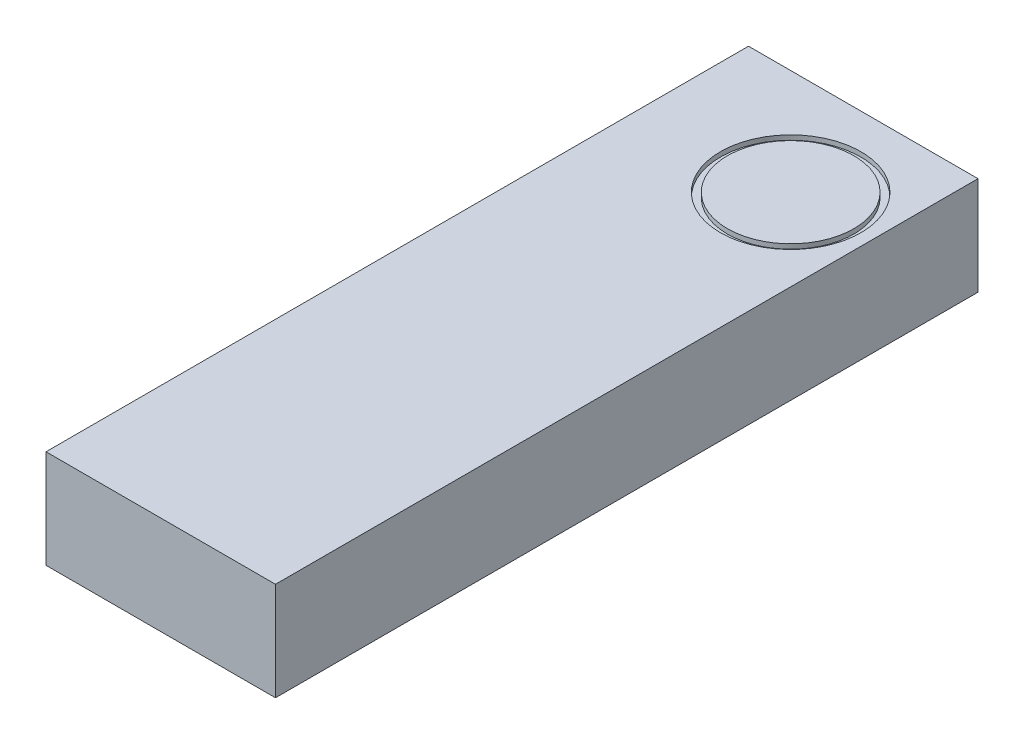
SolidWorks part; units mm, degrees
ref_plane "Plano frontal" through (0, 0, 0) normal (0, 0, 1) x (1, 0, 0)
ref_plane "Plano superior" through (0, 0, 0) normal (0, 1, 0) x (1, 0, 0)
ref_plane "Plano direito" through (0, 0, 0) normal (1, 0, 0) x (0, 0, -1)
sketch "Esboço1" plane through (0, 0, 0) normal (0, 1, 0) x (1, 0, 0)
  line L1 (-49, 150) -> (49, 150)
  line L2 (-49, 150) -> (-49, -150)
  line L3 (-49, -150) -> (49, -150)
  line L4 (49, 150) -> (49, -150)
  line L5 (-49, 150) -> (49, -150) construction
  line L6 (-49, -150) -> (49, 150) construction
  point P0 (0, 0)
  dimension "D1" = 98
  dimension "D2" = 300
extrude "Ressalto-extrusão1" add sketch "Esboço1" along normal blind 42
sketch "Esboço2" plane through (0, 42, 0) normal (0, 1, 0) x (1, 0, 0)
  line L1 (49, 150) -> (14, 150) construction
  line L2 (49, 150) -> (49, 105) construction
  line L3 (49, 105) -> (14, 105) construction
  line L4 (14, 150) -> (14, 105) construction
  line L5 (49, 150) -> (14, 105) construction
  line L6 (49, 105) -> (14, 150) construction
  circle A0 centre (14, 105) radius 30
  circle A1 centre (14, 105) radius 27
  point P6 (31.5, 127.5)
  point P8 (0, 0)
  point P9 (0, 0)
  dimension "D1" = 60
  dimension "D2" = 45
  dimension "D3" = 35
  dimension "D4" = 3
extrude "Corte-extrusão1" cut sketch "Esboço2" against normal blind 2
